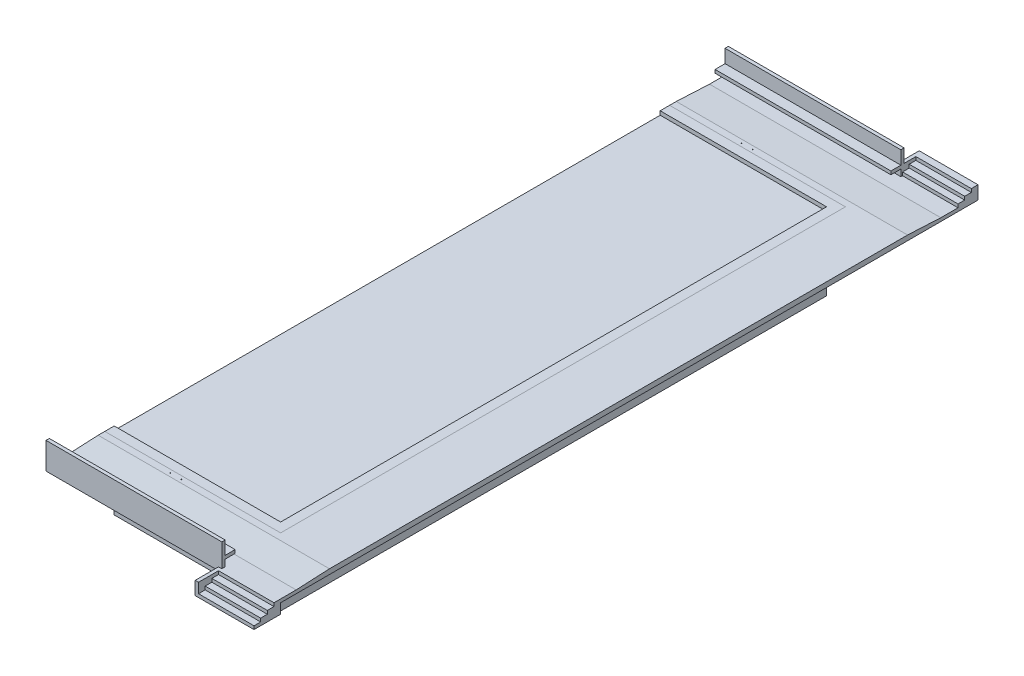
SolidWorks part; units mm, degrees
material "Water"
ref_plane "Front Plane" through (0, 0, 0) normal (0, 0, 1) x (1, 0, 0)
ref_plane "Top Plane" through (0, 0, 0) normal (0, 1, 0) x (1, 0, 0)
ref_plane "Right Plane" through (0, 0, 0) normal (1, 0, 0) x (0, 0, -1)
sketch "Sketch1" plane through (0, 0, 0) normal (0, 1, 0) x (1, 0, 0)
  line L1 (0, 0) -> (-7620, 0)
  line L2 (0, 0) -> (0, 25000.0008)
  line L3 (0, 25000.0008) -> (-7620, 25000.0008)
  line L4 (-7620, 0) -> (-7620, 25000.0008)
  dimension "D1" = 7620
  dimension "D2" = 25000.0008
extrude "Pool Water" add sketch "Sketch1" against normal blind 3352.8
sketch "Sketch2" plane through (0, 0, 0) normal (0, 1, 0) x (1, 0, 0)
  line L0 (-7620, 0) -> (-7620, -431.8)
  line L1 (-7620, -431.8) -> (431.8, -431.8)
  line L2 (431.8, -431.8) -> (431.8, 25431.8008)
  line L3 (431.8, 25431.8008) -> (-7620, 25431.8008)
  line L4 (-7620, 25431.8008) -> (-7620, 25000.0008)
  line L5 (0, 25000.0008) -> (-7620, 25000.0008) construction
  line L6 (0, 0) -> (0, 25000.0008) construction
  line L7 (-7620, 0) -> (0, 0)
  line L8 (0, 0) -> (0, 25000.0008)
  line L9 (0, 25000.0008) -> (-7620, 25000.0008)
  dimension "D1" = 431.8
  dimension "D2" = 431.8
  dimension "D3" = 431.8
extrude "Pool Deck Support" add sketch "Sketch2" along normal blind 101.6 and the other way blind 76.2 separate body
sketch "Sketch3" plane through (0, 101.6, 0) normal (0, 1, 0) x (1, 0, 0)
  line L0 (-7620, -2971.8) -> (-7620, -431.8)
  line L1 (-7620, -2971.8) -> (2971.8, -2971.8)
  line L3 (-7620, 27971.8008) -> (2971.8, 27971.8008)
  line L4 (2971.8, -2971.8) -> (2971.8, 27971.8008)
  line L5 (-7620, 25431.8008) -> (431.8, 25431.8008)
  line L6 (431.8, 25431.8008) -> (431.8, -431.8)
  line L7 (431.8, -431.8) -> (-7620, -431.8)
  line L8 (-7620, 25431.8008) -> (-7620, 27971.8008)
  dimension "D1" = 2540
  dimension "D2" = 2540
  dimension "D3" = 2540
extrude "Pool Deck" add sketch "Sketch3" against normal blind 152.4 separate body
sketch "Sketch4" plane through (0, -50.8, 0) normal (0, -1, 0) x (-1, 0, 0)
  line L0 (7620, -2971.8) -> (-2971.8, -2971.8) construction
  line L9 (-431.8, -3124.2) -> (7620, -3124.2)
  line L10 (-431.8, -3124.2) -> (-431.8, -2971.8)
  line L11 (-431.8, -2971.8) -> (7620, -2971.8)
  line L12 (7620, -3124.2) -> (7620, -2971.8)
  line L14 (7620, 27971.8008) -> (-431.8, 27971.8008)
  line L15 (7620, 27971.8008) -> (7620, 28124.2008)
  line L16 (7620, 28124.2008) -> (-431.8, 28124.2008)
  line L17 (-431.8, 27971.8008) -> (-431.8, 28124.2008)
  dimension "D1" = 152.4
  dimension "D2" = 152.4
  dimension "D3" = 8051.8
  dimension "D4" = 8051.8
extrude "Wall" add sketch "Sketch4" against normal blind 1219.2 separate body
sketch "Sketch7" plane through (0, 0, 2971.8) normal (0, 0, -1) x (-1, 0, 0)
  line L0 (-431.8, -50.8) -> (-431.8, 1168.4) construction
  line L1 (-431.8, 406.4) -> (7620, 406.4)
  line L2 (-431.8, 406.4) -> (-431.8, 558.8)
  line L3 (-431.8, 558.8) -> (7620, 558.8)
  line L4 (7620, 406.4) -> (7620, 558.8)
  line L5 (7620, -50.8) -> (7620, 1168.4) construction
  line L6 (7620, -50.8) -> (-2971.8, -50.8) construction
  dimension "D1" = 457.2
  dimension "D2" = 152.4
extrude "Near Side Bench" add sketch "Sketch7" along normal blind 457.2
sketch "Sketch8" plane through (0, 0, -27971.8008) normal (0, 0, 1) x (1, 0, 0)
  line L0 (-7620, -50.8) -> (-7620, 1168.4) construction
  line L1 (-7620, 558.8) -> (431.8, 558.8)
  line L2 (-7620, 558.8) -> (-7620, 406.4)
  line L3 (-7620, 406.4) -> (431.8, 406.4)
  line L6 (2971.8, -50.8) -> (-7620, -50.8) construction
  line L7 (431.8, 558.8) -> (431.8, 406.4)
  dimension "D1" = 152.4
  dimension "D2" = 457.2
  dimension "D3" = 8051.8
extrude "Far Side Bench" add sketch "Sketch8" along normal blind 457.2
sketch "Sketch9" plane through (2971.8, 0, 0) normal (1, 0, 0) x (0, 0, -1)
  line L0 (-3276.6, -50.8) -> (-3581.4, -50.8)
  line L1 (-2971.8, 101.6) -> (-3276.6, 101.6)
  line L2 (-2971.8, 101.6) -> (-2971.8, -291.9463)
  line L4 (-3276.6, 101.6) -> (-3276.6, -50.8)
  line L7 (-3581.4, -50.8) -> (-3581.4, -203.2)
  line L8 (-3581.4, -203.2) -> (-3886.2, -203.2)
  line L11 (-3886.2, -203.2) -> (-3886.2, -355.6)
  line L12 (-3886.2, -355.6) -> (-4191, -355.6)
  line L14 (-4160.2907, -508) -> (-4191, -508)
  line L15 (-4191, -355.6) -> (-4191, -508)
  line L16 (-4160.2907, -508) -> (-2971.8, -508)
  line L17 (-2971.8, -508) -> (-2971.8, -291.9463)
  line L18 (-2971.8, -50.8) -> (-2971.8, 101.6) construction
  line L19 (-2971.8, 101.6) -> (27971.8008, 101.6) construction
  dimension "D1" = 304.8
  dimension "D2" = 152.4
  dimension "D3" = 304.8
  dimension "D4" = 152.4
  dimension "D5" = 304.8
  dimension "D6" = 152.4
  dimension "D7" = 304.8
  dimension "D8" = 152.4
extrude "Stairs Down" add sketch "Sketch9" against normal up to surface (2540 mm away) up to face at (431.8, 520.7, 2895.6)
sketch "Sketch14" plane through (431.8, 0, 0) normal (1, 0, 0) x (0, 0, -1)
  line L0 (-431.8, 101.6) -> (-431.8, 177.8)
  line L1 (-431.8, 177.8) -> (-736.6, 177.8)
  line L6 (-736.6, 177.8) -> (-2260.6, 101.6)
  line L7 (-2260.6, 101.6) -> (-431.8, 101.6)
  dimension "D1" = 304.8
  dimension "D2" = 1828.8
extrude "Sloped Pool Deck Near Side" add sketch "Sketch14" against normal up to surface (8051.8 mm away) and the other way up to surface (2540 mm away) up to face at (-7620, 436.88, 2402.84) other way up to face at (2971.8, -177.8, -1677.4668)
sketch "Sketch15" plane through (0, 0, 431.8) normal (0, 0, -1) x (-1, 0, 0)
  line L0 (-431.8, 101.6) -> (-431.8, 177.8)
  line L1 (-431.8, 177.8) -> (-1346.2, 177.8)
  line L2 (-1346.2, 101.6) -> (-2260.6, 101.6)
  line L4 (-1346.2, 101.6) -> (-431.8, 101.6)
  line L5 (-2971.8, 101.6) -> (-2260.6, 101.6)
  line L6 (-2971.8, 101.6) -> (-2971.8, 177.8)
  line L7 (-2971.8, 177.8) -> (-1346.2, 177.8)
sketch "Sketch17" plane through (-7620, 0, 0) normal (-1, 0, 0) x (0, 0, 1)
  line L0 (-25431.8008, 101.6) -> (-25431.8008, 177.8)
  line L1 (-25431.8008, 177.8) -> (-25736.6008, 177.8)
  line L3 (-27260.6008, 101.6) -> (-25736.6008, 177.8)
  line L5 (-25431.8008, -50.8) -> (-25431.8008, 101.6) construction
  line L6 (-27971.8008, 101.6) -> (-25000.0008, 101.6) construction
  line L7 (-27260.6008, 101.6) -> (-25431.8008, 101.6)
  dimension "D1" = 1828.8
  dimension "D2" = 304.8
extrude "Sloped Pool Deck Far Side" add sketch "Sketch17" against normal up to surface (10591.8 mm away) up to face at (2971.8, -98.425, -1016.8001)
extrude "Sloped Pool Deck Length" add sketch "Sketch15" along normal up to surface (25863.6008 mm away) up to face at (-2324.1, 139.7, -25431.8008)
sketch "Sketch19" plane through (0, 101.6, 0) normal (0, 1, 0) x (1, 0, 0)
  line L0 (-7620, 0) -> (-7620, -431.8)
  line L1 (-7620, -431.8) -> (-7620, -736.6) construction
  line L2 (-7620, -431.8) -> (431.8, -431.8) construction
  line L3 (-7620, -431.8) -> (431.8, -431.8)
  line L4 (431.8, -431.8) -> (431.8, 25431.8008)
  line L5 (431.8, 25431.8008) -> (431.8, -431.8) construction
  line L6 (431.8, 25431.8008) -> (-7620, 25431.8008)
  line L7 (-7620, 25431.8008) -> (-7620, 25000.0008)
  line L8 (-7620, 25000.0008) -> (-7620, 0) construction
  line L9 (-7620, 25000.0008) -> (0, 25000.0008)
  line L10 (0, 25000.0008) -> (0, 0)
  line L11 (0, 0) -> (-7620, 0)
extrude "Drain Correction" cut sketch "Sketch19" against normal through all
sketch "Sketch20" plane through (0, 177.8, 0) normal (0, 1, 0) x (1, 0, 0)
  line L0 (-7620, 0) -> (-7620, -431.8)
  line L1 (-7620, -431.8) -> (431.8, -431.8)
  line L2 (431.8, -431.8) -> (431.8, 25431.8008)
  line L3 (431.8, 25431.8008) -> (-7620, 25431.8008)
  line L4 (431.8, 25431.8008) -> (-7620, 25431.8008) construction
  line L5 (-7620, 25431.8008) -> (-7620, 25000.0008)
  line L6 (-7620, 25000.0008) -> (-7620, 0) construction
  line L7 (-7620, 25000.0008) -> (0, 25000.0008)
  line L8 (0, 25000.0008) -> (0, 0)
  line L9 (0, 0) -> (-7620, 0)
sketch "Sketch21" plane through (2971.8, 0, 0) normal (1, 0, 0) x (0, 0, -1)
  line L0 (28657.6008, 406.4) -> (28352.8008, 406.4)
  line L1 (28962.4008, 558.8) -> (28657.6008, 558.8)
  line L3 (28657.6008, 558.8) -> (28657.6008, 406.4)
  line L4 (28352.8008, 406.4) -> (28352.8008, 254)
  line L5 (28352.8008, 254) -> (28048.0008, 254)
  line L6 (28048.0008, 254) -> (28048.0008, 101.6)
  line L7 (28048.0008, 101.6) -> (27743.2008, 101.6)
  line L9 (27743.2008, 101.6) -> (27743.2008, -50.8)
  line L12 (28962.4008, 558.8) -> (28962.4008, -50.8)
  line L13 (27743.2008, -50.8) -> (28962.4008, -50.8)
  dimension "D1" = 304.8
  dimension "D2" = 152.4
  dimension "D3" = 304.8
  dimension "D4" = 152.4
  dimension "D5" = 304.8
  dimension "D6" = 152.4
  dimension "D7" = 304.8
  dimension "D8" = 152.4
extrude "Stairs Up" add sketch "Sketch21" against normal up to surface (2540 mm away) up to face at (431.8, 520.7, -27895.6008)
extrude "Perimeter Drain" add sketch "Sketch20" against normal blind 228.6 separate body
sketch "Sketch23" plane through (0, 0, -25000.0008) normal (0, 0, 1) x (1, 0, 0)
  line L0 (0, -50.8) -> (0, 177.8) construction
  line L1 (-7620, 177.8) -> (0, 177.8) construction
  circle A0 centre (-5207, 25.4) radius 3.175
  circle A1 centre (-787.4, 25.4) radius 3.175
  dimension "D1" = 6.35
  dimension "D2" = 6.35
  dimension "D3" = 787.4
  dimension "D4" = 5207
  dimension "D5" = 152.4
  dimension "D6" = 152.4
extrude "Far Side Swim Lane Eyelets" cut sketch "Sketch23" against normal blind 152.4
sketch "Sketch25" plane through (0, 0, 0) normal (0, 0, -1) x (-1, 0, 0)
  line L0 (0, -50.8) -> (0, 177.8) construction
  line L1 (0, 177.8) -> (7620, 177.8) construction
  circle A0 centre (787.4, 25.4) radius 3.175
  circle A1 centre (5207, 25.4) radius 3.175
  dimension "D1" = 6.35
  dimension "D2" = 6.35
  dimension "D3" = 787.4
  dimension "D4" = 5207
  dimension "D5" = 152.4
  dimension "D6" = 152.4
extrude "Near Side Swim Lane Eyelets" cut sketch "Sketch25" against normal blind 152.4
sketch "Sketch26" plane through (431.8, 0, 0) normal (-1, 0, 0) x (0, 0, 1)
  line L1 (-28962.4008, 558.8) -> (-28124.2008, 558.8)
  line L2 (-28962.4008, 558.8) -> (-28962.4008, -50.8)
  line L3 (-28962.4008, -50.8) -> (-28124.2008, -50.8)
  line L4 (-28124.2008, 558.8) -> (-28124.2008, -50.8)
extrude "Far Side Stairs Wall" add sketch "Sketch26" along normal blind 152.4
sketch "Sketch27" plane through (431.8, 0, 0) normal (-1, 0, 0) x (0, 0, 1)
  line L1 (4191, -508) -> (3124.2, -508)
  line L2 (4191, -508) -> (4191, 101.6)
  line L3 (4191, 101.6) -> (3124.2, 101.6)
  line L4 (3124.2, -508) -> (3124.2, 101.6)
extrude "Near Side Stairs Wall" add sketch "Sketch27" along normal blind 152.4
sketch "Sketch28" plane through (0, 0, -27971.8008) normal (0, 0, 1) x (1, 0, 0)
  line L0 (431.8, 406.4) -> (431.8, 101.6) construction
  line L1 (-1397, 203.2) -> (-1295.4, 203.2)
  line L2 (-1397, 203.2) -> (-1397, 330.2)
  line L3 (-1397, 330.2) -> (-1295.4, 330.2)
  line L4 (-1295.4, 203.2) -> (-1295.4, 330.2)
  line L5 (431.8, 101.6) -> (-7620, 101.6) construction
  dimension "D1" = 127
  dimension "D2" = 101.6
  dimension "D3" = 1727.2
  dimension "D4" = 101.6
extrude "Far Side Electrical Box" add sketch "Sketch28" along normal blind 76.2 separate body
sketch "Sketch29" plane through (0, 0, -27895.6008) normal (0, 0, 1) x (1, 0, 0)
  line L0 (-1295.4, 330.2) -> (-1397, 330.2) construction
  line L1 (-1358.9, 304.8) -> (-1333.5, 304.8)
  line L2 (-1358.9, 304.8) -> (-1358.9, 279.4)
  line L3 (-1358.9, 228.6) -> (-1333.5, 228.6)
  line L4 (-1333.5, 304.8) -> (-1333.5, 279.4)
  line L5 (-1295.4, 203.2) -> (-1295.4, 330.2) construction
  line L6 (-1358.9, 254) -> (-1333.5, 254)
  line L7 (-1333.5, 279.4) -> (-1358.9, 279.4)
  line L8 (-1333.5, 254) -> (-1333.5, 228.6)
  line L9 (-1358.9, 254) -> (-1358.9, 228.6)
  dimension "D1" = 25.4
  dimension "D2" = 76.2
  dimension "D3" = 25.4
  dimension "D4" = 38.1
  dimension "D5" = 25.4
  dimension "D6" = 25.4
extrude "Far Side Outlets" add sketch "Sketch29" along normal blind 6.35 separate body
sketch "Sketch30" plane through (0, 0, 2971.8) normal (0, 0, -1) x (-1, 0, 0)
  line L0 (-431.8, 406.4) -> (-431.8, 101.6) construction
  line L1 (2108.2, 330.2) -> (2209.8, 330.2)
  line L2 (2108.2, 330.2) -> (2108.2, 203.2)
  line L3 (2108.2, 203.2) -> (2209.8, 203.2)
  line L4 (2209.8, 330.2) -> (2209.8, 203.2)
  line L5 (7620, 101.6) -> (-431.8, 101.6) construction
  dimension "D1" = 101.6
  dimension "D2" = 127
  dimension "D3" = 2540
  dimension "D4" = 101.6
extrude "Near Side Electrical Box" add sketch "Sketch30" along normal blind 76.2 separate body
sketch "Sketch31" plane through (0, 0, 2895.6) normal (0, 0, -1) x (-1, 0, 0)
  line L0 (2146.3, 304.8) -> (2171.7, 304.8)
  line L1 (2146.3, 304.8) -> (2146.3, 279.4)
  line L2 (2146.3, 228.6) -> (2171.7, 228.6)
  line L3 (2171.7, 304.8) -> (2171.7, 279.4)
  line L4 (2146.3, 254) -> (2171.7, 254)
  line L5 (2171.7, 279.4) -> (2146.3, 279.4)
  line L6 (2171.7, 254) -> (2171.7, 228.6)
  line L7 (2146.3, 254) -> (2146.3, 228.6)
  line L8 (2108.2, 330.2) -> (2108.2, 203.2) construction
  line L9 (2209.8, 330.2) -> (2108.2, 330.2) construction
  dimension "D1" = 25.4
  dimension "D2" = 76.2
  dimension "D3" = 25.4
  dimension "D4" = 25.4
  dimension "D5" = 38.1
  dimension "D6" = 25.4
extrude "Near Side Outlets" add sketch "Sketch31" along normal blind 6.35 separate body
sketch "Sketch32" plane through (0, 177.8, 0) normal (0, 1, 0) x (1, 0, 0)
  line L0 (0, 0) -> (-7620, 0) construction
  line L1 (0, 0) -> (0, 25000.0008) construction
  line L2 (0, 25000.0008) -> (0, 0) construction
  line L3 (-7620, 25000.0008) -> (0, 25000.0008) construction
  circle A0 centre (-4470.4, -584.2) radius 19.05
  circle A1 centre (-3962.4, -584.2) radius 19.05
  circle A2 centre (-4470.4, 25584.2008) radius 19.05
  circle A3 centre (-3962.4, 25584.2008) radius 19.05
  dimension "D1" = 508
  dimension "D4" = 38.1
  dimension "D5" = 38.1
  dimension "D7" = 38.1
  dimension "D8" = 38.1
  dimension "D2" = 584.2
  dimension "D3" = 3962.4
  dimension "D6" = 508
  dimension "D9" = 3962.4
  dimension "D10" = 584.2
extrude "Cut-Extrude4" cut sketch "Sketch32" against normal blind 152.4
